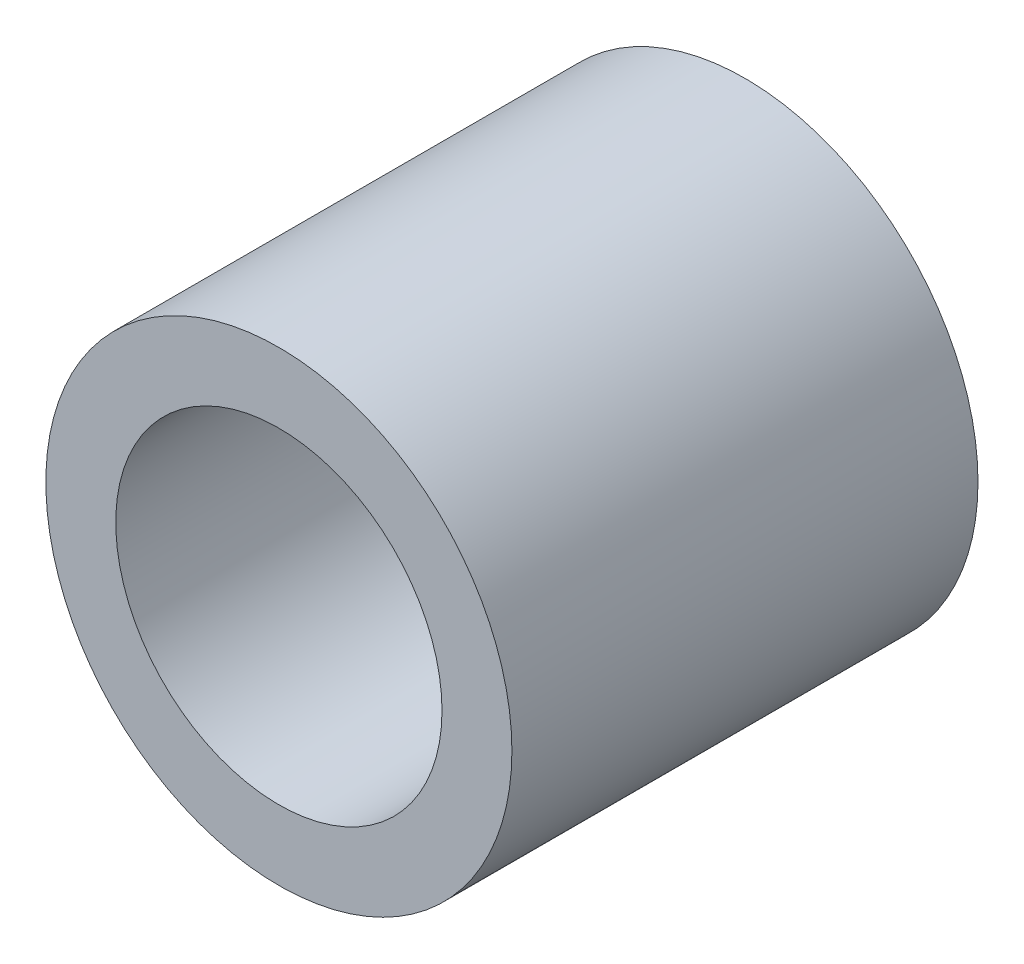
SolidWorks part; units mm, degrees
ref_plane "Front Plane" through (0, 0, 0) normal (0, 0, 1) x (1, 0, 0)
ref_plane "Top Plane" through (0, 0, 0) normal (0, 1, 0) x (1, 0, 0)
ref_plane "Right Plane" through (0, 0, 0) normal (1, 0, 0) x (0, 0, -1)
sketch "Sketch1" plane through (0, 0, 0) normal (0, 0, 1) x (1, 0, 0)
  circle A0 centre (0, 0) radius 6.35
  circle A1 centre (0, 0) radius 4.445
  dimension "D1" = 8.89
  dimension "D2" = 12.7
extrude "Boss-Extrude1" add sketch "Sketch1" along normal mid plane 12.7
